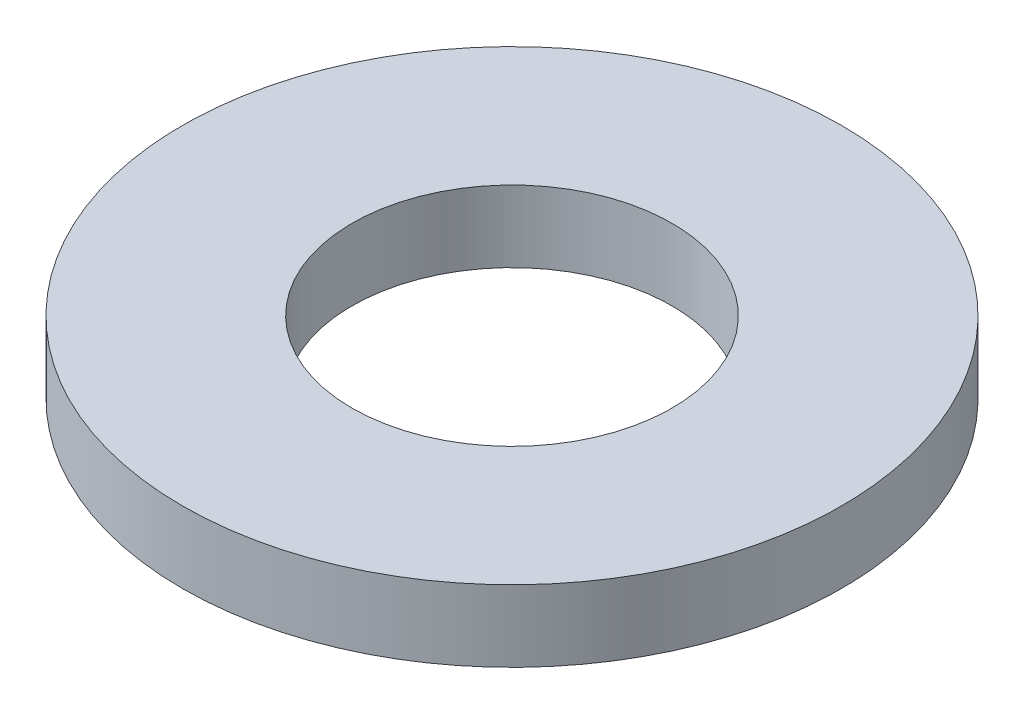
SolidWorks part; units mm, degrees
ref_plane "Front Plane" through (0, 0, 0) normal (0, 0, 1) x (1, 0, 0)
ref_plane "Top Plane" through (0, 0, 0) normal (0, 1, 0) x (1, 0, 0)
ref_plane "Right Plane" through (0, 0, 0) normal (1, 0, 0) x (0, 0, -1)
sketch "Sketch1" plane through (0, 0, 0) normal (0, 1, 0) x (1, 0, 0)
  circle A0 centre (0, 0) radius 87.5
  dimension "FLANGE_OD" = 175
extrude "Boss-Extrude1" add sketch "Sketch1" along normal blind 19
sketch "Sketch2" plane through (0, 0, 0) normal (0, 1, 0) x (1, 0, 0)
  circle A0 centre (0, 0) radius 42.5
  dimension "BORE_D" = 85
extrude "Cut-Extrude1" cut sketch "Sketch2" along normal through all
sketch "Sketch3" plane through (0, 19, 0) normal (0, 1, 0) x (1, 0, 0)
  circle A0 centre (0, 0) radius 30.1489 construction
  circle A1 centre (-30.1489, 0) radius 5.2485
  dimension "BOLT_D" = 10.497
  dimension "BOLT_PCD" = 60.2977
extrude "Cut-Extrude2" cut sketch "Sketch3" against normal blind 15.6484 rebuild error yes
pattern_circular "CirPattern1" count 5 over 360 rebuild error yes
